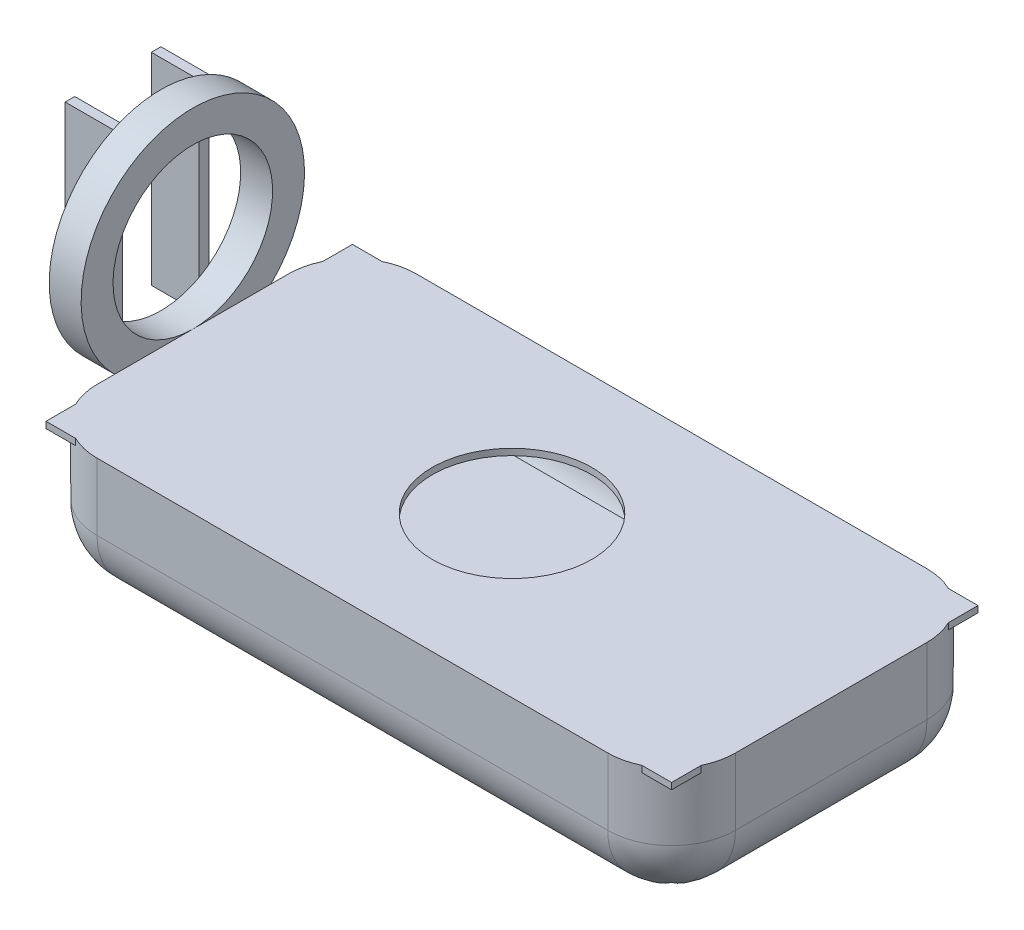
SolidWorks part; units mm, degrees
ref_plane "Front Plane" through (0, 0, 0) normal (0, 0, 1) x (1, 0, 0)
ref_plane "Top Plane" through (0, 0, 0) normal (0, 1, 0) x (1, 0, 0)
ref_plane "Right Plane" through (0, 0, 0) normal (1, 0, 0) x (0, 0, -1)
sketch "Sketch1" plane through (0, 0, 0) normal (0, 1, 0) x (1, 0, 0)
  line L1 (-46.4024, 68.2616) -> (153.5976, 68.2616)
  line L2 (-46.4024, 68.2616) -> (-46.4024, -31.7384)
  line L3 (-46.4024, -31.7384) -> (153.5976, -31.7384)
  line L4 (153.5976, 68.2616) -> (153.5976, -31.7384)
  dimension "D1" = 100
  dimension "D2" = 200
extrude "Boss-Extrude1" add sketch "Sketch1" along normal blind 50
fillet "Fillet3" radius 20 4 edges at (53.5976, 0, 31.7384) (153.5976, 0, -18.2616) (53.5976, 0, -68.2616) (-46.4024, 0, -18.2616)
fillet "Fillet4" radius 20 8 edges at (153.5976, 35, 31.7384) (153.5976, 35, -68.2616) (-46.4024, 35, -68.2616) (-46.4024, 35, 31.7384) (147.7397, 5.8579, 25.8806) (147.7397, 5.8579, -62.4037) (-40.5445, 5.8579, -62.4037) (-40.5445, 5.8579, 25.8806)
sketch "Sketch2" plane through (0, 0, 0) normal (0, -1, 0) x (-1, 0, 0)
  line L1 (36.4024, -21.7384) -> (-143.5976, -21.7384)
  line L2 (36.4024, -21.7384) -> (36.4024, 58.2616)
  line L3 (36.4024, 58.2616) -> (-143.5976, 58.2616)
  line L4 (-143.5976, -21.7384) -> (-143.5976, 58.2616)
  dimension "D1" = 10
  dimension "D2" = 10
  dimension "D3" = 10
  dimension "D4" = 10
extrude "Cut-Extrude2" cut sketch "Sketch2" against normal blind 10
shell "Shell1" thickness 2 removed face at (53.5976, 50, -18.2616)
sketch "Sketch3" plane through (0, 12, 0) normal (0, 1, 0) x (1, 0, 0)
  line L1 (57.5851, 14.0839) -> (53.1163, 14.0839)
  line L2 (57.5851, 14.0839) -> (57.5851, 18.8331)
  line L3 (57.5851, 18.8331) -> (53.1163, 18.8331)
  line L4 (53.1163, 14.0839) -> (53.1163, 18.8331)
extrude "Boss-Extrude2" add sketch "Sketch3" along normal blind 20
sketch "Sketch4" plane through (0, 32, 0) normal (0, 1, 0) x (1, 0, 0)
  line L0 (151.5976, -11.7384) -> (151.5976, 48.2616) construction
  line L1 (141.5976, -19.7384) -> (-34.4024, -19.7384)
  line L2 (141.5976, -19.7384) -> (141.5976, 56.2616)
  line L3 (141.5976, 56.2616) -> (-34.4024, 56.2616)
  line L4 (-34.4024, -19.7384) -> (-34.4024, 56.2616)
  line L5 (-44.4024, 48.2616) -> (-44.4024, -11.7384) construction
  line L6 (133.5976, 66.2616) -> (-26.4024, 66.2616) construction
  line L7 (-26.4024, -29.7384) -> (133.5976, -29.7384) construction
  dimension "D1" = 10
  dimension "D2" = 10
  dimension "D3" = 10
  dimension "D4" = 10
extrude "Boss-Extrude3" add sketch "Sketch4" along normal blind 2
sketch "Sketch5" plane through (0, 10, 0) normal (0, -1, 0) x (-1, 0, 0)
  line L1 (-143.5976, -21.7384) -> (36.4024, -21.7384)
  line L2 (-143.5976, -21.7384) -> (-143.5976, 58.2616)
  line L3 (-143.5976, 58.2616) -> (36.4024, 58.2616)
  line L4 (36.4024, -21.7384) -> (36.4024, 58.2616)
extrude "Cut-Extrude3" cut sketch "Sketch5" against normal blind 2
sketch "Sketch6" plane through (53.1163, 0, 0) normal (-1, 0, 0) x (0, 0, 1)
  line L1 (-14.0839, 32) -> (-18.8331, 32)
  line L2 (-14.0839, 32) -> (-14.0839, 12)
  line L3 (-14.0839, 12) -> (-18.8331, 12)
  line L4 (-18.8331, 32) -> (-18.8331, 12)
extrude "Cut-Extrude4" cut sketch "Sketch6" against normal blind 5
sketch "Sketch7" plane through (0, 32, 0) normal (0, -1, 0) x (-1, 0, 0)
  line L0 (34.4024, -19.7384) -> (-141.5976, -19.7384) construction
  line L1 (34.4024, 56.2616) -> (-141.5976, 56.2616)
  line L2 (34.4024, 56.2616) -> (34.4024, -19.7384)
  line L3 (34.4024, -19.7384) -> (-141.5976, -19.7384)
  line L4 (-141.5976, 56.2616) -> (-141.5976, -19.7384)
extrude "Boss-Extrude4" add sketch "Sketch7" along normal blind 15
sketch "Sketch8" plane through (0, 34, 0) normal (0, 1, 0) x (1, 0, 0)
  line L1 (-34.4024, 56.2616) -> (141.5976, 56.2616)
  line L2 (-34.4024, 56.2616) -> (-34.4024, -19.7384)
  line L3 (-34.4024, -19.7384) -> (141.5976, -19.7384)
  line L4 (141.5976, 56.2616) -> (141.5976, -19.7384)
extrude "Cut-Extrude5" cut sketch "Sketch8" against normal blind 15
sketch "Sketch9" plane through (0, 19, 0) normal (0, 1, 0) x (1, 0, 0)
  line L0 (-34.4024, 56.2616) -> (-34.4024, -19.7384) construction
  line L1 (-24.4024, 46.2616) -> (-14.4024, 46.2616)
  line L2 (-24.4024, 46.2616) -> (-24.4024, 36.2616)
  line L3 (-24.4024, 36.2616) -> (-14.4024, 36.2616)
  line L4 (-14.4024, 46.2616) -> (-14.4024, 36.2616)
  line L5 (-26.4024, 0.2616) -> (-16.4024, 0.2616)
  line L6 (-26.4024, 0.2616) -> (-26.4024, -9.7384)
  line L7 (-26.4024, -9.7384) -> (-16.4024, -9.7384)
  line L8 (-16.4024, 0.2616) -> (-16.4024, -9.7384)
  line L9 (121.5976, -9.7384) -> (131.5976, -9.7384)
  line L10 (121.5976, -9.7384) -> (121.5976, 0.2616)
  line L11 (121.5976, 0.2616) -> (131.5976, 0.2616)
  line L12 (131.5976, -9.7384) -> (131.5976, 0.2616)
  line L13 (121.5976, 38.2616) -> (131.5976, 38.2616)
  line L14 (121.5976, 38.2616) -> (121.5976, 48.2616)
  line L15 (121.5976, 48.2616) -> (131.5976, 48.2616)
  line L16 (131.5976, 38.2616) -> (131.5976, 48.2616)
  line L17 (141.5976, 56.2616) -> (-34.4024, 56.2616) construction
  line L18 (-36.4024, 58.2616) -> (143.5976, 58.2616) construction
  line L19 (141.5976, -19.7384) -> (141.5976, 56.2616) construction
  line L20 (-34.4024, -19.7384) -> (141.5976, -19.7384) construction
  line L21 (-36.4024, -21.7384) -> (-36.4024, 58.2616) construction
  point P20 (-12.1183, 56.2616)
  dimension "D1" = 10
  dimension "D2" = 10
  dimension "D3" = 10
  dimension "D4" = 10
  dimension "D5" = 10
  dimension "D6" = 10
  dimension "D7" = 10
  dimension "D8" = 10
  dimension "D9" = 10
  dimension "D10" = 10
  dimension "D11" = 10
  dimension "D12" = 10
  dimension "D13" = 10
  dimension "D14" = 10
  dimension "D15" = 10
  dimension "D16" = 10
extrude "Boss-Extrude5" add sketch "Sketch9" along normal blind 20
sketch "Sketch10" plane through (0, 39, 0) normal (0, 1, 0) x (1, 0, 0)
  line L0 (-44.4024, 48.2616) -> (-44.4024, -11.7384) construction
  line L1 (-44.4024, 66.2616) -> (151.5976, 66.2616)
  line L2 (-44.4024, 66.2616) -> (-44.4024, -29.7384)
  line L3 (-44.4024, -29.7384) -> (151.5976, -29.7384)
  line L4 (151.5976, 66.2616) -> (151.5976, -29.7384)
  line L5 (151.5976, -11.7384) -> (151.5976, 48.2616) construction
  line L6 (-26.4024, -29.7384) -> (133.5976, -29.7384) construction
  dimension "D1" = 0
  dimension "D2" = 0
  dimension "D3" = 0
  dimension "D4" = 0
extrude "Boss-Extrude6" add sketch "Sketch10" along normal blind 2
sketch "Sketch11" plane through (0, 41, 0) normal (0, 1, 0) x (1, 0, 0)
  line L1 (-51.7718, 74.9077) -> (182.32, 74.9077)
  line L2 (-51.7718, 74.9077) -> (-51.7718, -48.1338)
  line L3 (-51.7718, -48.1338) -> (182.32, -48.1338)
  line L4 (182.32, 74.9077) -> (182.32, -48.1338)
extrude "Cut-Extrude6" cut sketch "Sketch11" along normal blind 100
sketch "Sketch12" plane through (0, 41, 0) normal (0, 1, 0) x (1, 0, 0)
  line L0 (-26.4024, -31.7384) -> (133.5976, -31.7384) construction
  line L1 (133.5976, 68.2616) -> (-26.4024, 68.2616) construction
  line L2 (-46.4024, 48.2616) -> (-46.4024, -11.7384) construction
  line L3 (153.5976, -11.7384) -> (153.5976, 48.2616) construction
  circle A0 centre (53.5976, 18.2616) radius 25
  point P6 (-46.4024, 18.2616)
  point P11 (82.4648, 24.7669)
  dimension "D1" = 50
  dimension "D5" = 50
  dimension "D2" = 50
  dimension "D3" = 100
  dimension "D4" = 100
extrude "Cut-Extrude7" cut sketch "Sketch12" against normal blind 4
sketch "Sketch14" plane through (-46.4024, 0, 0) normal (-1, 0, 0) x (0, 0, 1)
  line L1 (-48.2616, 41) -> (11.7384, 41) construction
  circle A0 centre (-18.2616, 66) radius 35
  circle A1 centre (-18.2616, 66) radius 25
  point P2 (-18.2616, 41)
  dimension "D1" = 50
  dimension "D3" = 70
  dimension "D4" = 50
  dimension "D2" = 25
extrude "Boss-Extrude8" add sketch "Sketch14" along normal blind 10
sketch "Sketch15" plane through (-56.4024, 0, 0) normal (-1, 0, 0) x (0, 0, 1)
  line L1 (-33.2616, 97.6228) -> (-30.2616, 97.6228)
  line L2 (-33.2616, 97.6228) -> (-33.2616, 34.3772)
  line L3 (-33.2616, 34.3772) -> (-30.2616, 34.3772)
  line L4 (-30.2616, 97.6228) -> (-30.2616, 34.3772)
  line L5 (-3.2616, 97.6228) -> (-6.2616, 97.6228)
  line L6 (-3.2616, 97.6228) -> (-3.2616, 34.3772)
  line L7 (-3.2616, 34.3772) -> (-6.2616, 34.3772)
  line L8 (-6.2616, 97.6228) -> (-6.2616, 34.3772)
  circle A0 centre (-18.2616, 66) radius 35 construction
  circle A1 centre (-18.2616, 66) radius 25 construction
  dimension "D1" = 3
  dimension "D2" = 15
  dimension "D3" = 35
  dimension "D4" = 35
  dimension "D5" = 3
extrude "Boss-Extrude9" add sketch "Sketch15" along normal blind 15
